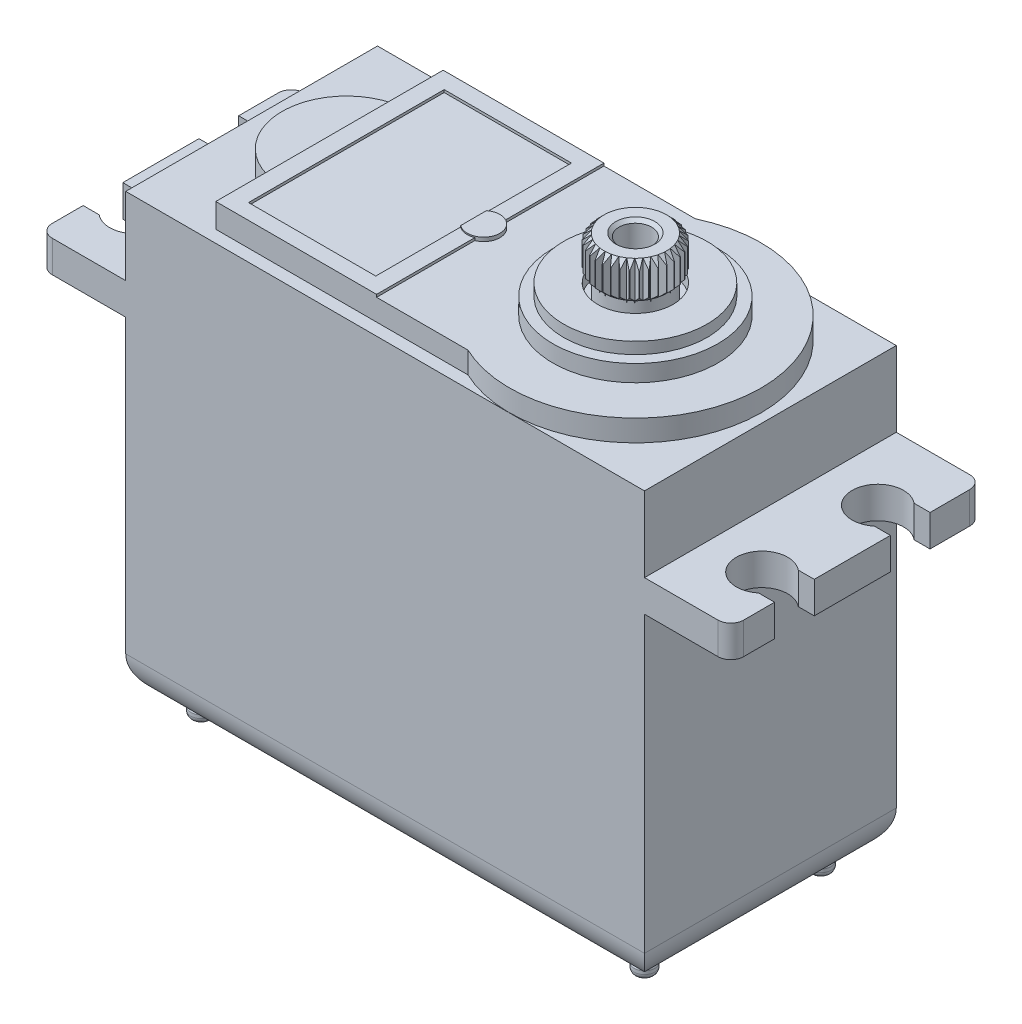
SolidWorks part; units mm, degrees
ref_plane "Front Plane" through (0, 0, 0) normal (0, 0, 1) x (1, 0, 0)
ref_plane "Top Plane" through (0, 0, 0) normal (0, 1, 0) x (1, 0, 0)
ref_plane "Right Plane" through (0, 0, 0) normal (1, 0, 0) x (0, 0, -1)
sketch "Sketch1" plane through (0, 0, 0) normal (0, 1, 0) x (1, 0, 0)
  line L1 (-18.6567, 11.3793) -> (21.6633, 11.3793)
  line L2 (-18.6567, 11.3793) -> (-18.6567, -8.1907)
  line L3 (-18.6567, -8.1907) -> (21.6633, -8.1907)
  line L4 (21.6633, 11.3793) -> (21.6633, -8.1907)
extrude "Boss-Extrude1" add sketch "Sketch1" along normal blind 35.37
sketch "Sketch2" plane through (21.6633, 0, 0) normal (1, 0, 0) x (0, 0, -1)
  line L0 (-8.1907, 0) -> (-8.1907, 3)
  line L1 (-8.1907, 35.37) -> (-8.1907, 0) construction
  line L2 (-8.1907, 3) -> (-5.1907, 0)
  line L3 (-8.1907, 0) -> (11.3793, 0) construction
  line L4 (-5.1907, 0) -> (-8.1907, 0)
  line L5 (1.5943, 0) -> (1.5943, 35.37) construction
  line L6 (-8.1907, 35.37) -> (11.3793, 35.37) construction
  line L7 (8.3793, 0) -> (11.3793, 0)
  line L8 (11.3793, 3) -> (8.3793, 0)
  line L9 (11.3793, 0) -> (11.3793, 3)
extrude "Cut-Extrude1" cut sketch "Sketch2" against normal up to next
sketch "Sketch3" plane through (0, 0, 8.1907) normal (0, 0, 1) x (1, 0, 0)
  line L0 (21.6633, 0) -> (18.6633, 0)
  line L1 (-18.6567, 0) -> (21.6633, 0) construction
  line L2 (18.6633, 0) -> (21.6633, 3)
  line L3 (21.6633, 35.37) -> (21.6633, 3) construction
  line L4 (21.6633, 3) -> (21.6633, 0)
  line L5 (1.5033, 35.37) -> (1.5033, 0) construction
  line L6 (-18.6567, 35.37) -> (21.6633, 35.37) construction
  line L7 (-18.6567, 3) -> (-18.6567, 0)
  line L8 (-15.6567, 0) -> (-18.6567, 3)
  line L9 (-18.6567, 0) -> (-15.6567, 0)
extrude "Cut-Extrude2" cut sketch "Sketch3" against normal up to next
fillet "Fillet2" radius 3 4 edges at (21.6633, 3, -1.5943) (1.5033, 3, 8.1907) (-18.6567, 3, -1.5943) (1.5033, 3, -11.3793)
sketch "Sketch5" plane through (21.6633, 0, 0) normal (1, 0, 0) x (0, 0, -1)
  line L0 (1.5943, 35.37) -> (1.5943, 29.53) construction
  line L1 (-8.1907, 35.37) -> (11.3793, 35.37) construction
  line L2 (-8.1907, 29.53) -> (1.5943, 29.53)
  line L3 (-8.1907, 35.37) -> (-8.1907, 4.2426) construction
  line L4 (1.5943, 29.53) -> (11.3793, 29.53)
  line L5 (11.3793, 35.37) -> (11.3793, 4.2426) construction
  line L6 (11.3793, 29.53) -> (11.3793, 27.07)
  line L7 (11.3793, 27.07) -> (-8.1907, 27.07)
  line L8 (-8.1907, 27.07) -> (-8.1907, 29.53)
extrude "Boss-Extrude2" add sketch "Sketch5" along normal blind 6.71
sketch "Sketch7" plane through (-18.6567, 0, 0) normal (-1, 0, 0) x (0, 0, 1)
  line L0 (-1.5943, 35.37) -> (-1.5943, 29.3613) construction
  line L1 (-11.3793, 29.3613) -> (-1.5943, 29.3613)
  line L2 (-1.5943, 29.3613) -> (8.1907, 29.3613)
  line L3 (8.1907, 29.3613) -> (8.1907, 26.9013)
  line L4 (8.1907, 26.9013) -> (-11.3793, 26.9013)
  line L5 (-11.3793, 26.9013) -> (-11.3793, 29.3613)
  line L6 (-11.3793, 35.37) -> (8.1907, 35.37) construction
  line L7 (8.1907, 35.37) -> (8.1907, 4.2426) construction
  line L8 (-11.3793, 35.37) -> (-11.3793, 4.2426) construction
extrude "Boss-Extrude3" add sketch "Sketch7" along normal blind 6.71
sketch "Sketch8" plane through (0, 29.53, 0) normal (0, 1, 0) x (1, 0, 0)
  line L0 (28.3733, 1.5943) -> (-25.3667, 1.5943) construction
  line L1 (28.3733, 4.2104) -> (28.3733, 7.2943)
  line L2 (-25.3667, -8.1907) -> (-25.3667, 11.3793) construction
  line L3 (28.3733, -1.7057) -> (28.3733, -4.7896)
  line L4 (28.3733, -1.7057) -> (27.1303, -1.7057)
  line L5 (28.3733, 11.3793) -> (28.3733, -8.1907) construction
  line L6 (-25.3667, -4.7896) -> (-25.3667, -1.7057)
  line L7 (28.3733, 7.2943) -> (27.1303, 7.2943)
  line L8 (-25.3667, 7.2943) -> (-25.3667, 4.2104)
  line L9 (28.3733, 4.2104) -> (27.1303, 4.2104)
  line L10 (21.6633, 11.3793) -> (21.6633, -8.1907) construction
  line L11 (28.3733, -4.7896) -> (27.1303, -4.7896)
  line L13 (1.5033, 11.3793) -> (1.5033, -8.1907) construction
  line L14 (21.6633, 11.3793) -> (-18.6567, 11.3793) construction
  line L15 (-18.6567, -8.1907) -> (21.6633, -8.1907) construction
  line L24 (-25.3667, 4.2104) -> (-24.1237, 4.2104)
  line L26 (-25.3667, -4.7896) -> (-24.1237, -4.7896)
  line L28 (-25.3667, -1.7057) -> (-24.1237, -1.7057)
  line L30 (-25.3667, 7.2943) -> (-24.1237, 7.2943)
  arc A0 (27.1303, -1.7057) -> (27.1303, -4.7896) centre (25.8566, -3.2477) ccw
  arc A1 (27.1303, 4.2104) -> (27.1303, 7.2943) centre (25.8566, 5.7523) cw
  arc A4 (-24.1237, 4.2104) -> (-24.1237, 7.2943) centre (-22.85, 5.7523) ccw
  arc A5 (-24.1237, -1.7057) -> (-24.1237, -4.7896) centre (-22.85, -3.2477) cw
  dimension "D1" = 2
  dimension "D2" = 4.1933
  dimension "D3" = 5.467
  dimension "D4" = 4.085
  dimension "D5" = 13.085
extrude "Cut-Extrude3" cut sketch "Sketch8" against normal up to next
sketch "Sketch9" plane through (0, 35.37, 0) normal (0, 1, 0) x (1, 0, 0)
  line L0 (6.9933, -8.1907) -> (6.9933, -7.2426) construction
  line L1 (-18.6567, 6.4311) -> (-12.6067, 6.4311) construction
  line L2 (6.9933, 11.3793) -> (6.9933, 10.4311) construction
  line L3 (-18.6567, -3.2426) -> (-12.6067, -3.2426) construction
  line L4 (-18.6567, -8.1907) -> (-18.6567, 11.3793) construction
  line L5 (-18.6567, 1.5943) -> (21.6633, 1.5943) construction
  line L6 (-12.6067, 10.4311) -> (6.9933, 10.4311)
  line L7 (-18.6567, 11.3793) -> (-18.6567, -8.1907) construction
  line L8 (-12.6067, -7.2426) -> (-12.6067, -3.2426)
  line L9 (21.6633, -8.1907) -> (21.6633, 11.3793) construction
  line L10 (-12.6067, 10.4311) -> (-12.6067, 6.4311)
  line L11 (-12.6067, -7.2426) -> (6.9933, -7.2426)
  line L12 (21.6633, 1.5943) -> (20.9438, 1.5943) construction
  line L13 (21.6633, 11.3793) -> (-18.6567, 11.3793) construction
  arc A0 (6.9933, 10.4311) -> (6.9933, -7.2426) centre (11.1697, 1.5943) cw
  arc A1 (-12.6067, 6.4311) -> (-12.6067, -3.2426) centre (-11.2767, 1.5943) ccw
extrude "Boss-Extrude4" add sketch "Sketch9" along normal blind 1.67
sketch "Sketch10" plane through (0, 37.04, 0) normal (0, 1, 0) x (1, 0, 0)
  circle A1 centre (11.1697, 1.5943) radius 6.415
extrude "Boss-Extrude5" add sketch "Sketch10" along normal blind 1.3
sketch "Sketch11" plane through (0, 38.34, 0) normal (0, 1, 0) x (-1, 0, 0)
  circle A2 centre (-11.1697, -1.5943) radius 5.575
extrude "Boss-Extrude6" add sketch "Sketch11" along normal blind 0.9
sketch "Sketch12" plane through (0, 39.24, 0) normal (0, 1, 0) x (1, 0, 0)
  circle A1 centre (11.1697, 1.5943) radius 2.925
extrude "Cut-Extrude4" cut sketch "Sketch12" against normal blind 1
sketch "Sketch13" plane through (0, 38.24, 0) normal (0, 1, 0) x (-1, 0, 0)
  circle A0 centre (-11.1697, -1.5943) radius 2.425
extrude "Boss-Extrude7" add sketch "Sketch13" along normal blind 1.5
sketch "Sketch14" plane through (0, 39.74, 0) normal (0, 1, 0) x (1, 0, 0)
  circle A0 centre (11.1697, 1.5943) radius 2.925
extrude "Boss-Extrude8" add sketch "Sketch14" along normal blind 2.86
sketch "Sketch15" plane through (0, 42.6, 0) normal (0, 1, 0) x (1, 0, 0)
  circle A0 centre (11.1697, 1.5943) radius 1.27
extrude "Cut-Extrude5" cut sketch "Sketch15" against normal blind 7
sketch "Sketch16" plane through (0, 37.04, 0) normal (0, 1, 0) x (1, 0, 0)
  line L0 (-12.6067, -7.2426) -> (6.9933, -7.2426) construction
  line L1 (-12.6067, 10.4311) -> (-0.1067, 10.4311)
  line L2 (-12.6067, 10.4311) -> (-12.6067, -7.2426)
  line L3 (-12.6067, -7.2426) -> (-0.1067, -7.2426)
  line L4 (-0.1067, 10.4311) -> (-0.1067, -7.2426)
  line L5 (-6.3168, 9.1673) -> (-6.3567, 10.4311) construction
  line L6 (-11.2628, 9.1673) -> (-1.3708, 9.1673)
  line L7 (-11.2628, 9.1673) -> (-11.2628, -6.0433)
  line L8 (-11.2628, -6.0433) -> (-1.3708, -6.0433)
  line L9 (-1.3708, 9.1673) -> (-1.3708, 1.562)
  line L10 (-11.2628, 1.562) -> (-12.6067, 1.5943) construction
  line L11 (-1.3708, 1.562) -> (-0.1067, 1.5943) construction
  line L12 (-6.3168, -6.0433) -> (-6.3567, -7.2426) construction
  line L13 (-1.3708, 1.562) -> (-1.3708, -6.0433)
extrude "Boss-Extrude9" add sketch "Sketch16" along normal blind 0.2
sketch "Sketch17" plane through (0, 37.24, 0) normal (0, 1, 0) x (-1, 0, 0)
  line L0 (1.3708, -1.562) -> (1.3708, -2.562)
  line L1 (1.3708, 6.0433) -> (1.3708, -9.1673) construction
  line L2 (1.3708, -1.562) -> (1.3708, -0.562)
  arc A0 (1.3708, -2.562) -> (1.3708, -0.562) centre (0.592, -1.562) cw
extrude "Boss-Extrude10" add sketch "Sketch17" along normal blind 0.1 and the other way blind 0.5
sketch "Sketch19" plane through (0, 42.6, 0) normal (0, 1, 0) x (1, 0, 0)
  line L0 (10.8404, 4.5007) -> (11.3402, 4.5143) construction
  line L1 (11.3402, 4.5143) -> (11.0903, 4.0075)
  line L2 (11.0903, 4.0075) -> (10.8404, 4.5007)
  line L3 (11.0903, 4.5075) -> (11.0903, 4.0075) construction
  line L4 (10.8404, 4.5007) -> (10.7613, 4.6463)
  line L5 (11.3402, 4.5143) -> (11.4053, 4.6463)
  line L6 (10.7613, 4.6463) -> (11.4053, 4.6463)
  circle A3 centre (11.1697, 1.5943) radius 2.925 construction
  circle A4 centre (11.1697, 1.5943) radius 2.925 construction
extrude "Cut-Extrude11" cut sketch "Sketch19" against normal blind 3
sketch "Sketch21" plane through (0, 0, 0) normal (0, -1, 0) x (1, 0, 0)
  line L0 (1.5033, 5.1907) -> (1.5033, -8.3793) construction
  line L1 (20.7846, 7.3121) -> (17.7846, 7.3121)
  line L2 (20.7846, 7.3121) -> (20.7846, 4.3121)
  line L3 (20.7846, 4.3121) -> (17.7846, 4.3121)
  line L4 (17.7846, 7.3121) -> (17.7846, 4.3121)
  line L5 (-15.6567, 5.1907) -> (18.6633, 5.1907) construction
  line L6 (-15.6567, -8.3793) -> (18.6633, -8.3793) construction
  line L7 (-15.6567, -1.5943) -> (18.6633, -1.5943) construction
  line L8 (-15.6567, -8.3793) -> (-15.6567, 5.1907) construction
  line L9 (18.6633, -8.3793) -> (18.6633, 5.1907) construction
  line L10 (17.7846, -10.5006) -> (17.7846, -7.5006)
  line L11 (20.7846, -7.5006) -> (17.7846, -7.5006)
  line L12 (20.7846, -10.5006) -> (20.7846, -7.5006)
  line L13 (20.7846, -10.5006) -> (17.7846, -10.5006)
  line L14 (-17.778, -7.5006) -> (-14.778, -7.5006)
  line L15 (-14.778, -10.5006) -> (-14.778, -7.5006)
  line L16 (-14.778, 7.3121) -> (-14.778, 4.3121)
  line L17 (-17.778, 4.3121) -> (-14.778, 4.3121)
  line L18 (-17.778, -10.5006) -> (-14.778, -10.5006)
  line L19 (-17.778, -10.5006) -> (-17.778, -7.5006)
  line L20 (-17.778, 7.3121) -> (-17.778, 4.3121)
  line L21 (-17.778, 7.3121) -> (-14.778, 7.3121)
extrude "Cut-Extrude12" cut sketch "Sketch21" against normal blind 1
fillet "Fillet4" radius 1 4 edges at (-14.778, 0.5, -7.5006) (-14.778, 0.5, 4.3121) (17.7846, 0.5, -7.5006) (17.7846, 0.5, 4.3121)
fillet "Fillet5" radius 1 4 edges at (-25.3667, 28.1313, 8.1907) (-25.3667, 28.1313, -11.3793) (28.3733, 28.3, -11.3793) (28.3733, 28.3, 8.1907)
chamfer "Chamfer2" distance 0.5 angle 45 2 edges at (11.2493, 42.6, 1.3297) (11.2493, 39.74, 1.3297)
chamfer "Chamfer3" distance 0.25 angle 45 1 edges at (11.1697, 42.6, -0.3243)
pattern_circular "CirPattern12" count 34 over 360 about axis through (11.1697, 42.6, -1.5943) along (0, -1, 0) of "Cut-Extrude11"
sketch "Sketch23" plane through (0, 1, 0) normal (0, -1, 0) x (1, 0, 0)
  line L0 (1.5033, 5.1907) -> (1.5033, -8.3793) construction
  line L1 (-14.7854, 5.1907) -> (17.792, 5.1907) construction
  line L2 (-14.7854, -8.3793) -> (17.792, -8.3793) construction
  line L3 (18.6633, -1.5943) -> (-15.6567, -1.5943) construction
  line L4 (18.6633, -7.508) -> (18.6633, 4.3195) construction
  line L5 (-15.6567, -7.508) -> (-15.6567, 4.3195) construction
  circle A0 centre (18.7344, -8.4503) radius 0.4237
  circle A1 centre (18.7344, 5.2618) radius 0.4237
  circle A2 centre (-15.7278, 5.2618) radius 0.4237
  circle A3 centre (-15.7278, -8.4503) radius 0.4237
extrude "Boss-Extrude12" add sketch "Sketch23" along normal blind 0.1
sketch "Sketch24" plane through (0, 0.9, 0) normal (0, -1, 0) x (1, 0, 0)
  line L0 (1.5033, 5.1907) -> (1.5033, -8.3793) construction
  line L1 (-14.7854, 5.1907) -> (17.792, 5.1907) construction
  line L2 (-14.7854, -8.3793) -> (17.792, -8.3793) construction
  line L3 (18.6633, -1.5943) -> (-15.6567, -1.5943) construction
  line L4 (18.6633, -7.508) -> (18.6633, 4.3195) construction
  line L5 (-15.6567, -7.508) -> (-15.6567, 4.3195) construction
  circle A0 centre (18.7344, -8.4503) radius 0.8
  circle A1 centre (18.7344, 5.2618) radius 0.8
  circle A2 centre (-15.7278, 5.2618) radius 0.8
  circle A3 centre (-15.7278, -8.4503) radius 0.8
extrude "Boss-Extrude13" add sketch "Sketch24" along normal blind 0.9
fillet "Fillet8" radius 0.45 4 edges at (18.7344, 0, -9.2503) (-15.7278, 0, -7.6503) (-15.7278, 0, 4.4618) (18.7344, 0, 6.0618)
fillet "Fillet9" radius 0.2 4 edges at (-15.7278, 0.9, -7.6503) (-15.7278, 0.9, 4.4618) (18.7344, 0.9, 6.0618) (18.7344, 0.9, -9.2503)
sketch "Sketch25" plane through (0, 0, 0) normal (0, -1, 0) x (1, 0, 0)
  line L0 (18.0844, 5.3868) -> (18.0844, 5.1368)
  line L1 (18.6094, 4.6118) -> (18.8594, 4.6118)
  line L2 (18.0844, 5.3868) -> (18.6094, 5.3868)
  line L3 (18.6094, 5.3868) -> (18.6094, 5.9118)
  line L4 (19.3844, 5.1368) -> (19.3844, 5.3868)
  line L5 (18.8594, 5.9118) -> (18.6094, 5.9118)
  line L6 (1.5033, 5.1907) -> (1.5033, -8.3793) construction
  line L7 (-14.7854, 5.1907) -> (17.792, 5.1907) construction
  line L8 (-14.7854, -8.3793) -> (17.792, -8.3793) construction
  line L9 (18.6633, -1.5943) -> (-15.6567, -1.5943) construction
  line L10 (18.6633, -7.508) -> (18.6633, 4.3195) construction
  line L11 (-15.6567, -7.508) -> (-15.6567, 4.3195) construction
  line L12 (18.6094, -8.3253) -> (18.0844, -8.3253)
  line L13 (18.6094, -7.8003) -> (18.6094, -8.3253)
  line L14 (18.8594, -8.3253) -> (18.8594, -7.8003)
  line L15 (19.3844, -8.3253) -> (18.8594, -8.3253)
  line L16 (18.8594, -8.5753) -> (19.3844, -8.5753)
  line L17 (18.8594, 5.9118) -> (18.8594, 5.3868)
  line L18 (18.8594, 5.3868) -> (19.3844, 5.3868)
  line L19 (18.8594, -9.1003) -> (18.8594, -8.5753)
  line L20 (19.3844, 5.1368) -> (18.8594, 5.1368)
  line L21 (18.8594, 5.1368) -> (18.8594, 4.6118)
  line L22 (18.8594, -9.1003) -> (18.6094, -9.1003)
  line L23 (18.6094, 4.6118) -> (18.6094, 5.1368)
  line L24 (18.6094, 5.1368) -> (18.0844, 5.1368)
  line L25 (19.3844, -8.3253) -> (19.3844, -8.5753)
  line L26 (18.6094, -8.5753) -> (18.6094, -9.1003)
  line L27 (18.0844, -8.5753) -> (18.6094, -8.5753)
  line L28 (18.6094, -7.8003) -> (18.8594, -7.8003)
  line L29 (18.0844, -8.5753) -> (18.0844, -8.3253)
  line L30 (-15.0778, -8.5753) -> (-15.0778, -8.3253)
  line L31 (-15.6028, -7.8003) -> (-15.8528, -7.8003)
  line L32 (-15.0778, -8.5753) -> (-15.6028, -8.5753)
  line L33 (-15.6028, -8.5753) -> (-15.6028, -9.1003)
  line L34 (-16.3778, -8.3253) -> (-16.3778, -8.5753)
  line L35 (-15.6028, 5.1368) -> (-15.0778, 5.1368)
  line L36 (-15.6028, 4.6118) -> (-15.6028, 5.1368)
  line L37 (-15.8528, -9.1003) -> (-15.6028, -9.1003)
  line L38 (-15.8528, 5.1368) -> (-15.8528, 4.6118)
  line L39 (-16.3778, 5.1368) -> (-15.8528, 5.1368)
  line L40 (-15.8528, -9.1003) -> (-15.8528, -8.5753)
  line L41 (-15.8528, 5.3868) -> (-16.3778, 5.3868)
  line L42 (-15.8528, 5.9118) -> (-15.8528, 5.3868)
  line L43 (-15.8528, -8.5753) -> (-16.3778, -8.5753)
  line L44 (-16.3778, -8.3253) -> (-15.8528, -8.3253)
  line L45 (-15.8528, -8.3253) -> (-15.8528, -7.8003)
  line L46 (-15.6028, -7.8003) -> (-15.6028, -8.3253)
  line L47 (-15.6028, -8.3253) -> (-15.0778, -8.3253)
  line L48 (-15.8528, 5.9118) -> (-15.6028, 5.9118)
  line L49 (-16.3778, 5.1368) -> (-16.3778, 5.3868)
  line L50 (-15.6028, 5.3868) -> (-15.6028, 5.9118)
  line L51 (-15.0778, 5.3868) -> (-15.6028, 5.3868)
  line L52 (-15.6028, 4.6118) -> (-15.8528, 4.6118)
  line L53 (-15.0778, 5.3868) -> (-15.0778, 5.1368)
extrude "Cut-Extrude14" cut sketch "Sketch25" against normal blind 0.6
